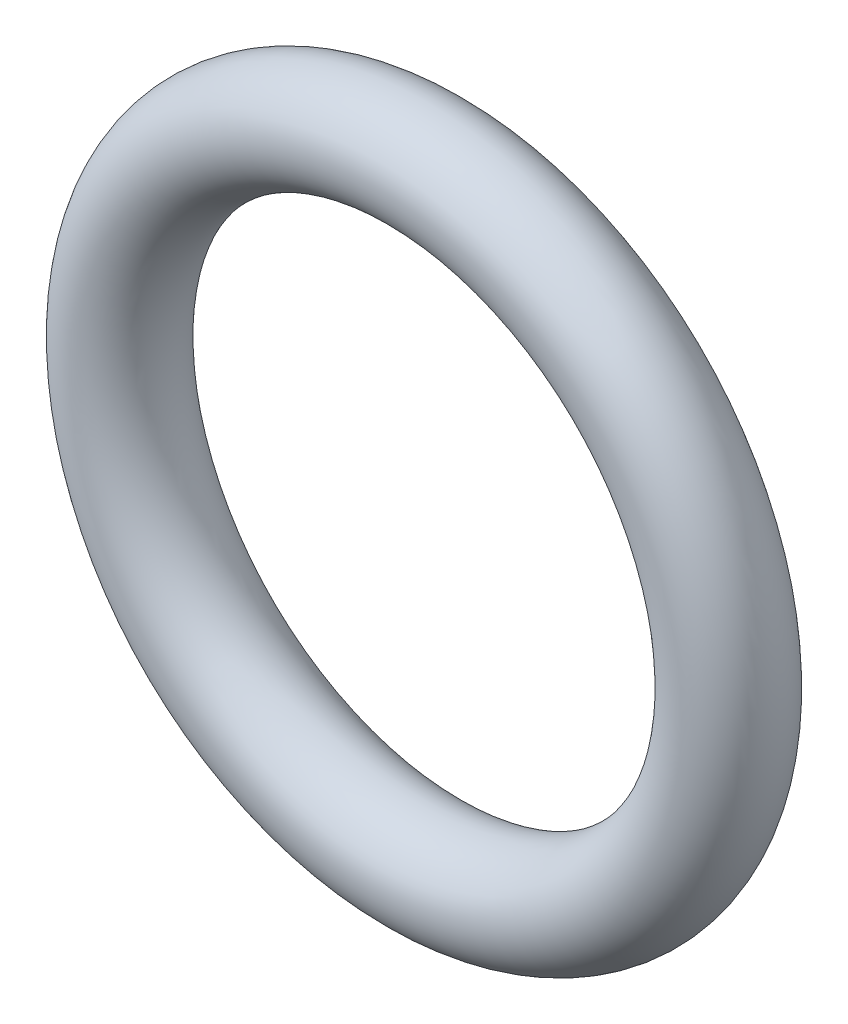
SolidWorks part; units mm, degrees
ref_plane "Front Plane" through (0, 0, 0) normal (0, 0, 1) x (1, 0, 0)
ref_plane "Top Plane" through (0, 0, 0) normal (0, 1, 0) x (1, 0, 0)
ref_plane "Right Plane" through (0, 0, 0) normal (1, 0, 0) x (0, 0, -1)
sketch "Sketch1" plane through (0, 0, 0) normal (1, 0, 0) x (0, 0, -1)
  circle A0 centre (0, 0) radius 2.282
  dimension "D1" = 4.5641
sketch "Sketch2" plane through (0, 0, 0) normal (0, 0, 1) x (1, 0, 0)
  circle A0 centre (0, -13.3945) radius 13.3945
  dimension "D1" = 26.7891
sweep "Sweep1" add profiles "Sketch1" path "Sketch2"
sketch "Sketch3" plane through (0, 0, 0) normal (0, 0, 1) x (1, 0, 0)
  line L0 (-11.1125, -13.3945) -> (11.1125, -13.3945) construction
  line L1 (0, -2.282) -> (0, -24.507) construction
  circle A0 centre (0, -13.3945) radius 11.1125 construction
  point P0 (-4.7625, -23.4348)
  point P1 (4.7625, -23.4348)
  point P5 (-7.7771, -5.457)
  point P6 (7.7771, -5.457)
  point P7 (0, 0)
  point P8 (0, 0)
  point P11 (0, 0)
  point P12 (0, 0)
  point P13 (0, 0)
  point P17 (0, 0)
  point P18 (0, 0)
  point P19 (0, 0)
  dimension "D1" = 9.525
  dimension "D2" = 15.5543
ref_point "Point1"
ref_point "Point2"
ref_point "Point3"
ref_point "Point4"
ref_axis "Axis1" through (7.7771, -5.457, 0) along (-1, 0, 0)
ref_axis "Axis2" through (4.7625, -23.4348, 0) along (-1, 0, 0)
